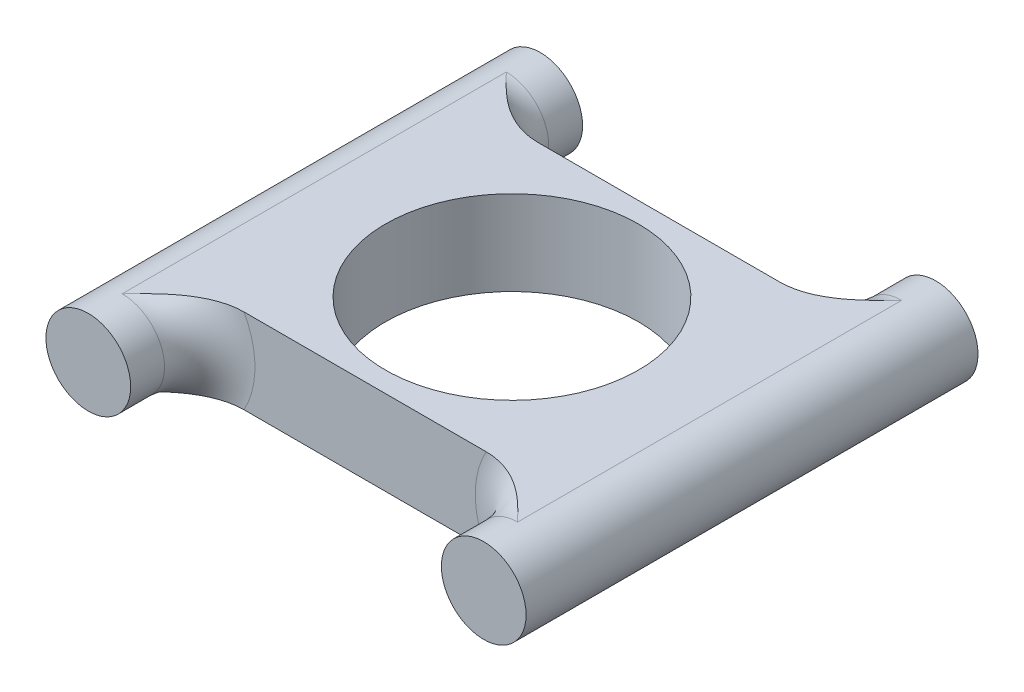
SolidWorks part; units mm, degrees
ref_plane "Front Plane" through (0, 0, 0) normal (0, 0, 1) x (1, 0, 0)
ref_plane "Top Plane" through (0, 0, 0) normal (0, 1, 0) x (1, 0, 0)
ref_plane "Right Plane" through (0, 0, 0) normal (1, 0, 0) x (0, 0, -1)
sketch "Sketch1" plane through (0, 0, 0) normal (0, 0, 1) x (1, 0, 0)
  line L1 (-22.225, 4.7625) -> (22.225, 4.7625)
  line L2 (-22.225, 4.7625) -> (-22.225, -4.7625)
  line L3 (-22.225, -4.7625) -> (22.225, -4.7625)
  line L4 (22.225, 4.7625) -> (22.225, -4.7625)
  line L5 (-22.225, 4.7625) -> (22.225, -4.7625) construction
  line L6 (-22.225, -4.7625) -> (22.225, 4.7625) construction
  circle A0 centre (-22.225, 0) radius 4.7625
  circle A1 centre (22.225, 0) radius 4.7625
  point P0 (0, 0)
  dimension "D1" = 44.45
  dimension "D2" = 9.525
extrude "Boss-Extrude1" add sketch "Sketch1" along normal blind 25.4 and the other way blind 25.4 contours L4 A1 | L4 A1 | A0 region at (24.2463, 0, 0) region at (20.2037, 0, 0)
sketch "Sketch2" plane through (0, 0, 0) normal (0, 1, 0) x (1, 0, 0)
  circle A0 centre (0, 0) radius 14.224
  dimension "D1" = 28.448
extrude "Boss-Extrude2" add sketch "Sketch1<3>" along normal blind 16.51 and the other way blind 16.51 contours A1 L1 A0 L3 region at (0, 0, 0)
sketch "Sketch1<3>" plane through (0, 0, 0) normal (0, 0, 1) x (1, 0, 0) same geometry as "Sketch1"
extrude "Cut-Extrude1" cut sketch "Sketch2" against normal blind 16.51 and the other way blind 16.51 contours A0
fillet "Fillet1" radius 5.08 4 edges at (-17.4625, 0, -16.51) (17.4625, 0, -16.51) (17.4625, 0, 16.51) (-17.4625, 0, 16.51)
